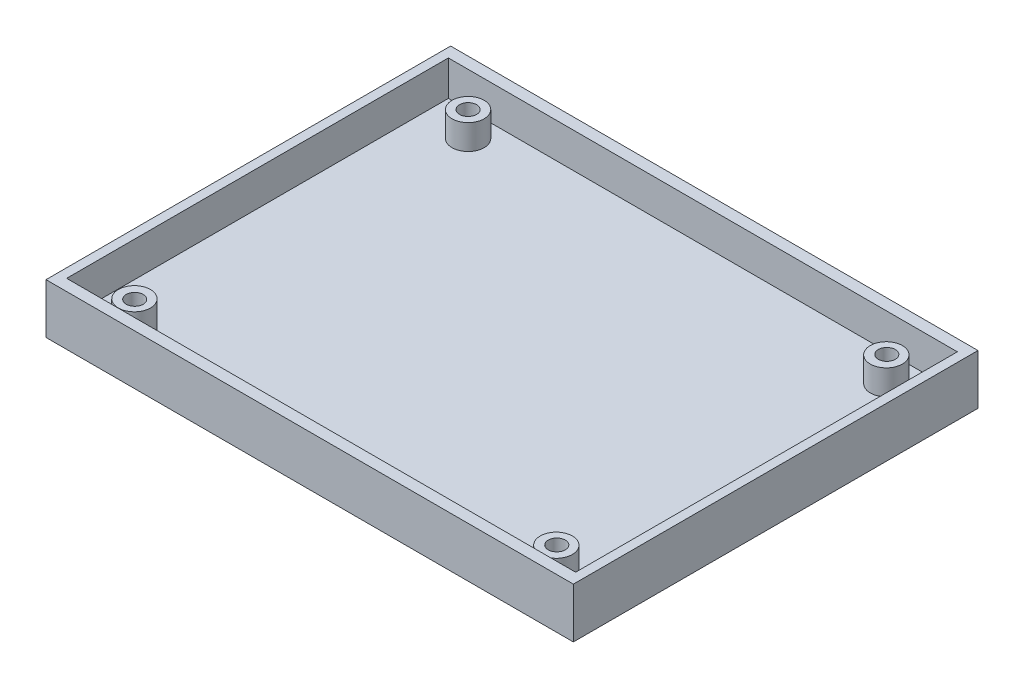
SolidWorks part; units mm, degrees
ref_plane "Front Plane" through (0, 0, 0) normal (0, 0, 1) x (1, 0, 0)
ref_plane "Top Plane" through (0, 0, 0) normal (0, 1, 0) x (1, 0, 0)
ref_plane "Right Plane" through (0, 0, 0) normal (1, 0, 0) x (0, 0, -1)
sketch "Sketch1" plane through (0, 0, 0) normal (0, 1, 0) x (1, 0, 0)
  line L1 (-50.8, -38.1) -> (50.8, -38.1)
  line L2 (-50.8, -38.1) -> (-50.8, 38.1)
  line L3 (-50.8, 38.1) -> (50.8, 38.1)
  line L4 (50.8, -38.1) -> (50.8, 38.1)
  line L5 (-50.8, -38.1) -> (50.8, 38.1) construction
  line L6 (-50.8, 38.1) -> (50.8, -38.1) construction
  line L7 (-41.91, -33.147) -> (41.91, -33.147) construction
  line L8 (-41.91, -33.147) -> (-41.91, 33.147) construction
  line L9 (-41.91, 33.147) -> (41.91, 33.147) construction
  line L10 (41.91, -33.147) -> (41.91, 33.147) construction
  line L11 (-41.91, -33.147) -> (41.91, 33.147) construction
  line L12 (-41.91, 33.147) -> (41.91, -33.147) construction
  line L13 (-52.6322, -40.3845) -> (52.6322, -40.3845)
  line L14 (-52.6322, -40.3845) -> (-52.6322, 40.3845)
  line L15 (-52.6322, 40.3845) -> (52.6322, 40.3845)
  line L16 (52.6322, -40.3845) -> (52.6322, 40.3845)
  line L17 (-52.6322, -40.3845) -> (52.6322, 40.3845) construction
  line L18 (-52.6322, 40.3845) -> (52.6322, -40.3845) construction
  circle A0 centre (-41.91, 33.147) radius 1.7
  circle A1 centre (42.2051, 32.6055) radius 1.7
  circle A2 centre (42.2051, -33.2675) radius 1.7
  circle A3 centre (-42.3706, -32.9365) radius 1.7
  circle A4 centre (-41.91, 33.147) radius 3.2013
  circle A5 centre (42.2259, 32.4942) radius 3.2013
  circle A6 centre (-42.5118, -32.8598) radius 3.2013
  circle A7 centre (42.2062, -33.3587) radius 3.2013
  point P0 (0, 0)
  point P6 (0, 0)
  point P15 (0, 0)
  point P21 (0, 0)
  point P27 (0, 0)
  point P28 (0, 0)
  point P29 (0, 0)
  point P30 (0, 0)
  point P33 (0, 0)
  point P36 (0, 0)
extrude "Boss-Extrude4" add sketch "Sketch1" along normal blind 3 contours L1 L4 L3 L2 A7 A6 A5 A4 region at (0, 0, -0.0024)
extrude "Boss-Extrude6" add sketch "Sketch1<8>" along normal blind 10 contours L13 L16 L15 L14 L4 L1 L2 L3 region at (-51.3054, 0, 0)
sketch "Sketch1<8>" plane through (0, 0, 0) normal (0, 1, 0) x (1, 0, 0) same geometry as "Sketch1"
extrude "Boss-Extrude7" add sketch "Sketch1<10>" along normal blind 8 contours A4 A0 | A7 A2 | A6 A3 | A5 A1 region at (-45.0207, 0, -33.147) region at (39.1152, 0, -32.4942) region at (-45.6225, 0, 32.8598) region at (39.0955, 0, 33.3587)
sketch "Sketch1<10>" plane through (0, 0, 0) normal (0, 1, 0) x (1, 0, 0) same geometry as "Sketch1"
